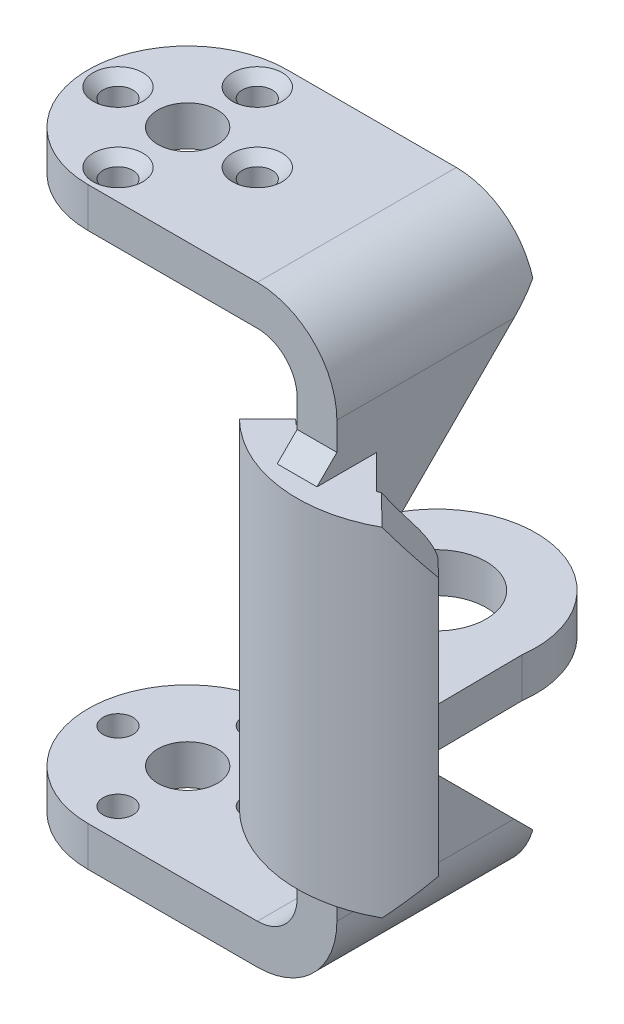
SolidWorks part; units mm, degrees
ref_plane "Спереди" through (0, 0, 0) normal (0, 0, 1) x (1, 0, 0)
ref_plane "Сверху" through (0, 0, 0) normal (0, 1, 0) x (1, 0, 0)
ref_plane "Справа" through (0, 0, 0) normal (1, 0, 0) x (0, 0, -1)
sketch "Sketch1" plane through (0, 0, 0) normal (0, 1, 0) x (1, 0, 0)
  line L1 (0, -10) -> (25, -10)
  line L2 (0, -10) -> (0, 10)
  line L3 (0, 10) -> (25, 10)
  line L4 (25, -10) -> (25, 10)
  circle A0 centre (0, 0) radius 10
  dimension "D1" = 20
  dimension "D2" = 20
  dimension "D3" = 25
extrude "Boss-Extrude1" add sketch "Sketch1" along normal blind 59.6 contours L2 A0 | L2 A0 | A0 L1 L4 L3 region at (16.2817, 0, 0) region at (-4.2441, 0, 0) region at (4.2441, 0, 0)
sketch "Sketch2" plane through (0, 0, 10) normal (0, 0, 1) x (1, 0, 0)
  line L0 (-10, 59.6) -> (-10, 0) construction
  line L1 (-10, 4) -> (21, 4)
  line L2 (-10, 4) -> (-10, 55.6)
  line L3 (-10, 55.6) -> (21, 55.6)
  line L4 (21, 4) -> (21, 55.6)
  line L5 (-10, 0) -> (0, 0) construction
  line L6 (0, 59.6) -> (-10, 59.6) construction
  line L7 (25, 59.6) -> (25, 0) construction
  dimension "D1" = 4
  dimension "D2" = 4
  dimension "D3" = 4
extrude "Cut-Extrude1" cut sketch "Sketch2" against normal blind 59.6
sketch "Sketch3" plane through (0, 59.6, 0) normal (0, 1, 0) x (1, 0, 0)
  circle A0 centre (0, 0) radius 7 construction
  circle A1 centre (-7, 0) radius 1.5
  circle A2 centre (0, 7) radius 1.5
  circle A3 centre (7, 0) radius 1.5
  circle A4 centre (0, -7) radius 1.5
  point P5 (0, 0)
  point P6 (0, 7)
  point P14 (0, 0)
  dimension "D1" = 14
  dimension "D2" = 3
  dimension "D3" = 4
extrude "Cut-Extrude2" cut sketch "Sketch3" against normal through all
chamfer "Chamfer1" distance 1 angle 45 8 edges at (-7, 0, 1.5) (0, 0, 8.5) (7, 0, 1.5) (0, 0, -5.5) (0, 59.6, -5.5) (7, 59.6, 1.5) (0, 59.6, 8.5) (-7, 59.6, 1.5)
sketch "Sketch4" plane through (0, 59.6, 0) normal (0, 1, 0) x (1, 0, 0)
  circle A0 centre (0, 0) radius 3
  dimension "D1" = 6
extrude "Cut-Extrude3" cut sketch "Sketch4" against normal through all
fillet "Fillet1" radius 4 2 edges at (21, 4, 0) (21, 55.6, 0)
sketch "Sketch6" plane through (25, 0, 0) normal (1, 0, 0) x (0, 0, -1)
  line L0 (10, 59.6) -> (10, 0) construction
  line L1 (30, 19.8) -> (-10, 19.8)
  line L2 (30, 19.8) -> (30, 39.8)
  line L3 (30, 39.8) -> (-10, 39.8)
  line L4 (-10, 19.8) -> (-10, 39.8)
  line L5 (30, 19.8) -> (-10, 39.8) construction
  line L6 (30, 39.8) -> (-10, 19.8) construction
  line L7 (-10, 59.6) -> (-10, 0) construction
  point P0 (10, 29.8)
  dimension "D1" = 20
extrude "Cut-Extrude4" cut sketch "Sketch6" against normal blind 59.6
ref_plane "Plane1" through (0, 29.8, 0) normal (0, -1, 0) x (-1, 0, 0)
sketch "Sketch5" plane through (0, 29.8, 0) normal (0, -1, 0) x (-1, 0, 0)
  line L1 (-25, -10) -> (-25, 10) construction
  circle A1 centre (-25, 0) radius 10
  dimension "D1" = 20
extrude "Boss-Extrude2" add sketch "Sketch5" along normal mid plane 4 separate body
sketch "Sketch8" plane through (0, 29.8, 0) normal (0, -1, 0) x (-1, 0, 0)
  line L0 (-25, -10) -> (-25, 10) construction
  line L1 (-18.0015, -7.1429) -> (-15.202, -10)
  line L2 (0, -10) -> (-25, -10) construction
  line L3 (-32.1429, -6.9985) -> (-35, -9.798)
  arc A0 (-32.1429, -6.9985) -> (-18.0015, -7.1429) centre (-25, 0) ccw
  arc A1 (-35, -9.798) -> (-15.202, -10) centre (-25, 0) ccw
  dimension "D1" = 28
extrude "Boss-Extrude3" add sketch "Sketch8" along normal mid plane 34
chamfer "Chamfer2" distance 4 angle 45 6 edges at (33.5714, 46.8, 8.3983) (33.5714, 12.8, 8.3983) (25, 43.3, 10) (25, 16.3, 10) (21, 16.3, 9.1652) (21, 43.3, 9.1652) first distance on face at (23.9426, 46.8, 9.7231) first distance on face at (33.0952, 29.8, 7.9317) first distance on face at (25, 49.12, 2) first distance on face at (24.0607, 18.3, 8.8256) first distance on face at (21, 46.0667, 3.0551)
chamfer "Chamfer3" distance 4 angle 45 1 edges at (32.1429, 29.8, 6.9985)
fillet "Fillet3" radius 2 2 edges at (32.1429, 37.3, 6.9985) (32.1429, 22.3, 6.9985)
chamfer "Chamfer4" distance 14 angle 45 2 edges at (23, 39.8, -10) (23, 19.8, -10)
chamfer "Chamfer5" distance 2 angle 45 2 edges at (23, 46.8, 10) (23, 12.8, 10)
fillet "Fillet4" radius 8 2 edges at (25, 0, 0) (25, 59.6, 0)
sketch "Sketch11" plane through (0, 27.8, 0) normal (0, -1, 0) x (1, 0, 0)
  circle A0 centre (25, 0) radius 5
  dimension "D1" = 10
extrude "Cut-Extrude5" cut sketch "Sketch11" against normal blind 4
